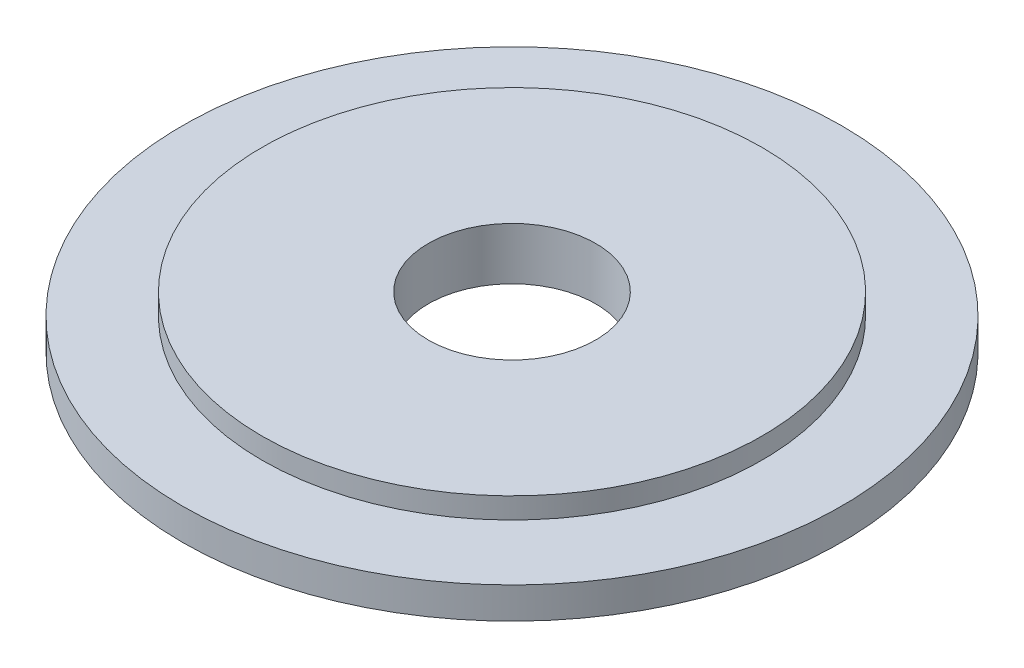
SolidWorks part; units mm, degrees
ref_plane "Front Plane" through (0, 0, 0) normal (0, 0, 1) x (1, 0, 0)
ref_plane "Top Plane" through (0, 0, 0) normal (0, 1, 0) x (1, 0, 0)
ref_plane "Right Plane" through (0, 0, 0) normal (1, 0, 0) x (0, 0, -1)
sketch "Croquis1" plane through (0, 0, 0) normal (0, 1, 0) x (1, 0, 0)
  circle A0 centre (0, 0) radius 23.9
  circle A1 centre (0, 0) radius 31.5
  circle A2 centre (0, 0) radius 8
  dimension "D1" = 47.8
  dimension "D2" = 63
  dimension "D3" = 16
extrude "Saliente-Extruir1" add sketch "Croquis1" along normal blind 2 contours A0 A2 region at (-23.224, 0, 0)
extrude "Saliente-Extruir2" add sketch "Croquis1<3>" against normal blind 3 contours A1 A0 | A0 A2 region at (-23.224, 0, 0) region at (-30.609, 0, 0)
sketch "Croquis1<3>" plane through (0, 0, 0) normal (0, 1, 0) x (1, 0, 0) same geometry as "Croquis1"
equation "\"ID\"= 47.8"
equation "\"D1@Croquis1\"=\"ID\""
equation "\"OD\"= 63"
equation "\"D2@Croquis1\"=\"OD\""
equation "\"Dmandril\"= 16"
equation "\"D3@Croquis1\"=\"Dmandril\""
